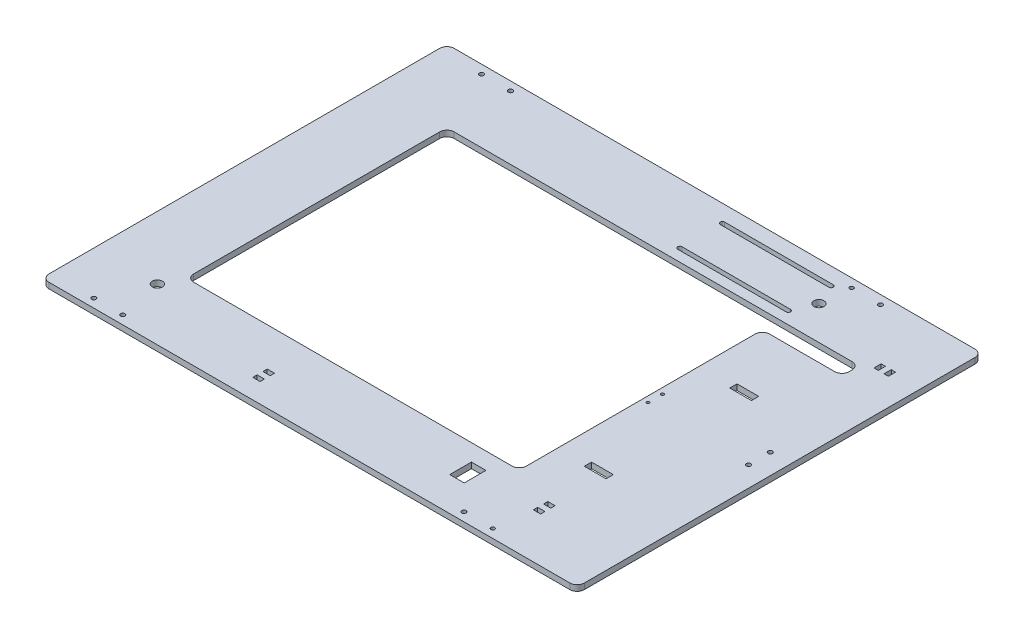
SolidWorks part; units mm, degrees
material "Pine"
ref_plane "Front Plane" through (0, 0, 0) normal (0, 0, 1) x (1, 0, 0)
ref_plane "Top Plane" through (0, 0, 0) normal (0, 1, 0) x (1, 0, 0)
ref_plane "Right Plane" through (0, 0, 0) normal (1, 0, 0) x (0, 0, -1)
sketch "Sketch1" plane through (0, 0, 0) normal (0, 1, 0) x (1, 0, 0)
  line L1 (0, 0) -> (370, 0)
  line L2 (0, 0) -> (0, 280)
  line L3 (0, 280) -> (370, 280)
  line L4 (370, 0) -> (370, 280)
  line L5 (50, 50) -> (280, 50)
  line L6 (50, 50) -> (50, 230)
  line L7 (50, 230) -> (280, 230)
  line L8 (280, 50) -> (280, 230)
  line L9 (50, 280) -> (50, 274) construction
  line L10 (50, 274) -> (30, 274) construction
  line L12 (185, 280) -> (185, 0) construction
  line L13 (0, 140) -> (370, 140) construction
  line L14 (284, 140) -> (284, 145) construction
  line L15 (284, 140) -> (284, 135) construction
  circle A0 centre (30, 274) radius 1.5
  circle A1 centre (50, 274) radius 1.5692
  circle A2 centre (30, 6) radius 1.5
  circle A3 centre (50, 6) radius 1.5
  circle A4 centre (285.7569, 273.9854) radius 1.3573
  circle A5 centre (305.7569, 273.9346) radius 1.5
  circle A6 centre (285.7569, 6.0015) radius 1.5
  circle A7 centre (305.7569, 6.0068) radius 1.3225
  circle A8 centre (284, 145) radius 1
  circle A9 centre (284, 135) radius 1
  dimension "D11" = 3
  dimension "D12" = 2
  dimension "D1" = 370
  dimension "D2" = 280
  dimension "D3" = 230
  dimension "D4" = 50
  dimension "D5" = 50
  dimension "D6" = 50
  dimension "D8" = 6
  dimension "D10" = 20
  dimension "D13" = 4
  dimension "D14" = 10
  dimension "D15" = 20
  dimension "D16" = 20
  dimension "D17" = 20
extrude "Boss-Extrude1" add sketch "Sketch1" along normal blind 4
sketch "Sketch2" plane through (0, 4, 0) normal (0, 1, 0) x (1, 0, 0)
  line L1 (280, 230) -> (335, 230)
  line L2 (280, 230) -> (280, 218)
  line L3 (280, 218) -> (335, 218)
  line L4 (335, 230) -> (335, 218)
  dimension "D1" = 55
  dimension "D2" = 12
extrude "Cut-Extrude1" cut sketch "Sketch2" against normal blind 10
sketch "Sketch3" plane through (0, 4, 0) normal (0, 1, 0) x (1, 0, 0)
  line L0 (356, 140) -> (356, 147.5) construction
  line L1 (370, 0) -> (370, 280) construction
  line L3 (356, 147.5) -> (356, 140) construction
  line L6 (356, 140) -> (356, 132.5) construction
  circle A0 centre (356, 147.5) radius 1.5
  circle A1 centre (356, 132.5) radius 1.5
  dimension "D1" = 3
  dimension "D2" = 3
  dimension "D3" = 14
  dimension "D4" = 15
extrude "Cut-Extrude2" cut sketch "Sketch3" against normal blind 10
sketch "Sketch4" plane through (0, 4, 0) normal (0, 1, 0) x (1, 0, 0)
  line L0 (277.5, 280) -> (277.5, 268) construction
  line L1 (370, 280) -> (0, 280) construction
  line L2 (277.5, 280) -> (277.5, 238.5) construction
  line L3 (277.5, 268) -> (202.5, 268) construction
  line L4 (277.5, 266.5) -> (202.5, 266.5)
  line L5 (277.5, 269.5) -> (202.5, 269.5)
  line L6 (277.5, 238.5) -> (202.5, 238.5) construction
  line L7 (277.5, 237) -> (202.5, 237)
  line L8 (277.5, 240) -> (202.5, 240)
  line L9 (370, 0) -> (370, 280) construction
  arc A0 (277.5, 266.5) -> (277.5, 269.5) centre (277.5, 268) ccw
  arc A1 (202.5, 269.5) -> (202.5, 266.5) centre (202.5, 268) ccw
  arc A2 (277.5, 237) -> (277.5, 240) centre (277.5, 238.5) ccw
  arc A3 (202.5, 240) -> (202.5, 237) centre (202.5, 238.5) ccw
  point P6 (240, 268)
  point P11 (240, 238.5)
  dimension "D1" = 12
  dimension "D2" = 41.5
  dimension "D3" = 3
  dimension "D4" = 3
  dimension "D5" = 75
  dimension "D6" = 130
extrude "Cut-Extrude3" cut sketch "Sketch4" against normal blind 10
fillet "Fillet3" radius 5 1 edges at (370, 2, 0)
fillet "Fillet4" radius 5 1 edges at (370, 2, -280)
fillet "Fillet5" radius 5 1 edges at (0, 2, 0)
fillet "Fillet6" radius 5 1 edges at (0, 2, -280)
fillet "Fillet7" radius 5 1 edges at (280, 2, -218)
fillet "Fillet8" radius 5 1 edges at (280, 2, -50)
fillet "Fillet9" radius 5 4 edges at (335, 2, -218) (335, 2, -230) (50, 2, -230) (50, 2, -50)
sketch "Sketch6" plane through (0, 0, 0) normal (0, -1, 0) x (1, 0, 0)
  line L0 (279, -268) -> (279, -238.5) construction
  circle A0 centre (283.8523, -253.25) radius 3.5
  arc A1 (277.5, -269.5) -> (277.5, -266.5) centre (277.5, -268) ccw construction
  arc A2 (277.5, -240) -> (277.5, -237) centre (277.5, -238.5) ccw construction
  point P10 (283.8523, -253.25)
  dimension "D1" = 7
extrude "Cut-Extrude4" cut sketch "Sketch6" against normal blind 10
sketch "Sketch7" plane through (0, 0, 0) normal (0, -1, 0) x (1, 0, 0)
  circle A0 centre (43.5283, -36.3572) radius 3.5
  point P0 (43.5283, -36.3572)
  point P3 (50, -30.5)
  dimension "D1" = 7
extrude "Cut-Extrude5" cut sketch "Sketch7" against normal blind 10
sketch "Sketch8" plane through (0, 0, 0) normal (0, -1, 0) x (1, 0, 0)
  line L1 (132.3588, -13.485) -> (137.3588, -13.485)
  line L2 (132.3588, -13.485) -> (132.3588, -16.485)
  line L3 (132.3588, -16.485) -> (137.3588, -16.485)
  line L4 (137.3588, -13.485) -> (137.3588, -16.485)
  line L5 (132.3588, -20.485) -> (137.3588, -20.485)
  line L6 (132.3588, -20.485) -> (132.3588, -23.485)
  line L7 (132.3588, -23.485) -> (137.3588, -23.485)
  line L8 (137.3588, -20.485) -> (137.3588, -23.485)
  line L9 (258.6011, -23.3631) -> (268.6011, -23.3631)
  line L10 (258.6011, -23.3631) -> (258.6011, -38.3631)
  line L11 (258.6011, -38.3631) -> (268.6011, -38.3631)
  line L12 (268.6011, -23.3631) -> (268.6011, -38.3631)
  line L20 (308.6025, -31.1591) -> (313.6025, -31.1591)
  line L21 (308.6025, -31.1591) -> (308.6025, -34.1591)
  line L22 (308.6025, -34.1591) -> (313.6025, -34.1591)
  line L23 (313.6025, -31.1591) -> (313.6025, -34.1591)
  line L24 (308.6025, -38.1591) -> (313.6025, -38.1591)
  line L25 (308.6025, -38.1591) -> (308.6025, -41.1591)
  line L26 (308.6025, -41.1591) -> (313.6025, -41.1591)
  line L27 (313.6025, -38.1591) -> (313.6025, -41.1591)
  line L28 (315.1261, -74.8595) -> (300.1261, -74.8595)
  line L29 (341.3593, -233.7592) -> (344.3593, -233.7592)
  line L30 (341.3593, -233.7592) -> (341.3593, -238.7592)
  line L31 (341.3593, -238.7592) -> (344.3593, -238.7592)
  line L32 (344.3593, -233.7592) -> (344.3593, -238.7592)
  line L33 (348.3593, -238.7592) -> (351.3593, -238.7592)
  line L34 (348.3593, -238.7592) -> (348.3593, -233.7592)
  line L35 (348.3593, -233.7592) -> (351.3593, -233.7592)
  line L36 (351.3593, -238.7592) -> (351.3593, -233.7592)
  line L37 (318.5539, -171.9384) -> (303.5539, -171.9384)
  line L38 (318.5539, -171.9384) -> (318.5539, -176.9384)
  line L39 (318.5539, -176.9384) -> (303.5539, -176.9384)
  line L40 (303.5539, -171.9384) -> (303.5539, -176.9384)
  line L41 (315.1261, -74.8595) -> (315.1261, -79.8595)
  line L42 (315.1261, -79.8595) -> (300.1261, -79.8595)
  line L43 (300.1261, -74.8595) -> (300.1261, -79.8595)
  point P8 (134.8588, -16.485)
  point P30 (311.1025, -34.1591)
  dimension "D1" = 5
  dimension "D2" = 3
  dimension "D3" = 4
  dimension "D4" = 15
  dimension "D5" = 10
  dimension "D6" = 4
  dimension "D7" = 5
  dimension "D8" = 3
  dimension "D9" = 5
  dimension "D10" = 3
  dimension "D11" = 4
  dimension "D12" = 5
  dimension "D13" = 15
  dimension "D14" = 5
  dimension "D15" = 15
extrude "Cut-Extrude6" cut sketch "Sketch8" against normal blind 10
